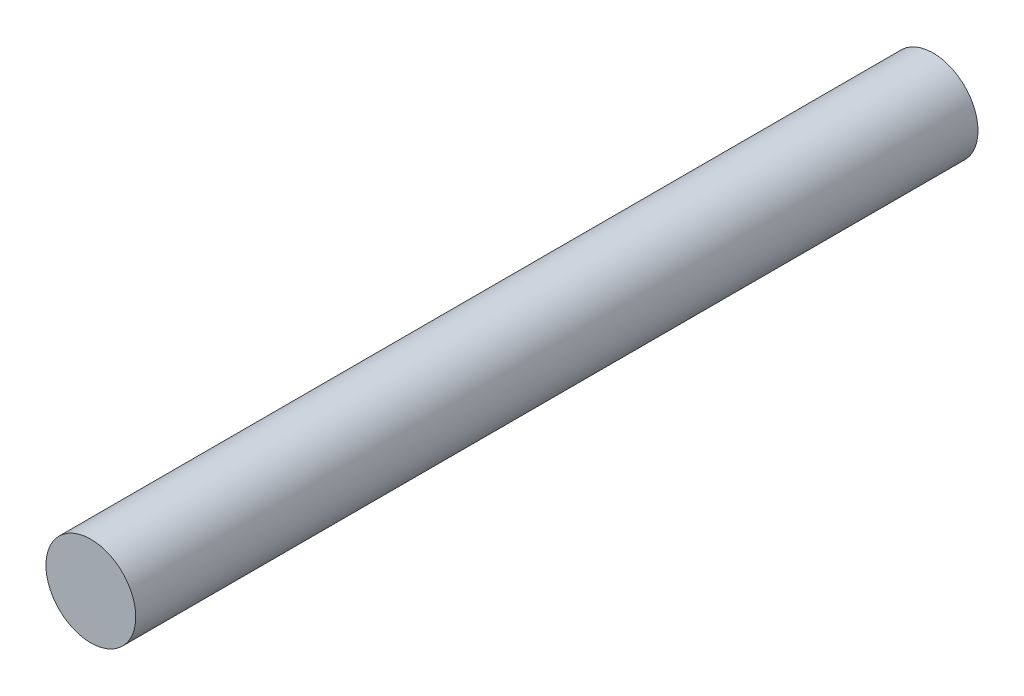
SolidWorks part; units mm, degrees
material "Brass"
ref_plane "Front Plane" through (0, 0, 0) normal (0, 0, 1) x (1, 0, 0)
ref_plane "Top Plane" through (0, 0, 0) normal (0, 1, 0) x (1, 0, 0)
ref_plane "Right Plane" through (0, 0, 0) normal (1, 0, 0) x (0, 0, -1)
sketch "Sketch1" plane through (0, 0, 0) normal (0, 0, 1) x (1, 0, 0)
  circle A0 centre (0, 0) radius 0.4
  dimension "D1" = 0.8
extrude "Boss-Extrude1" add sketch "Sketch1" along normal blind 7.5
scale "Scale1" scale about centroid uniform scaling yes scale factor 6
